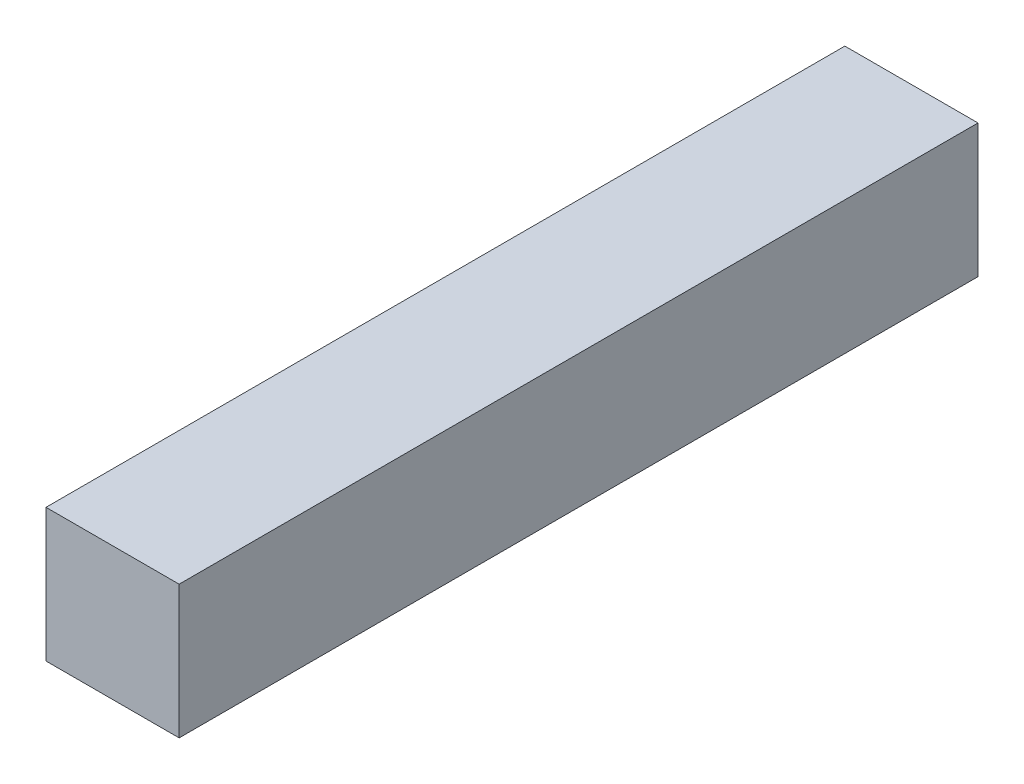
SolidWorks part; units mm, degrees
ref_plane "Front Plane" through (0, 0, 0) normal (0, 0, 1) x (1, 0, 0)
ref_plane "Top Plane" through (0, 0, 0) normal (0, 1, 0) x (1, 0, 0)
ref_plane "Right Plane" through (0, 0, 0) normal (1, 0, 0) x (0, 0, -1)
sketch "Sketch1" plane through (0, 0, 0) normal (0, 0, 1) x (1, 0, 0)
  line L3 (1.5, -1.5) -> (-1.5, -1.5)
  line L4 (1.5, -1.5) -> (1.5, 1.5)
  line L5 (1.5, 1.5) -> (-1.5, 1.5)
  line L6 (-1.5, -1.5) -> (-1.5, 1.5)
  line L7 (1.5, -1.5) -> (-1.5, 1.5) construction
  line L8 (1.5, 1.5) -> (-1.5, -1.5) construction
  point P0 (0, 0)
  dimension "Width" = 3
  dimension "Height" = 3
sketch "Sketch2" plane through (0, 0, 0) normal (1, 0, 0) x (0, 0, -1)
  line L2 (9, -1.5) -> (-9, -1.5)
  line L3 (9, -1.5) -> (9, 1.5)
  line L4 (9, 1.5) -> (-9, 1.5)
  line L5 (-9, -1.5) -> (-9, 1.5)
  line L6 (9, -1.5) -> (-9, 1.5) construction
  line L7 (9, 1.5) -> (-9, -1.5) construction
  point P0 (0, 0)
  point P4 (0, 0)
  point P15 (-5.7, 1.5)
  point P17 (5.7, 1.5)
  dimension "Length" = 18
  dimension "D1" = 3.3
  dimension "D2" = 3.3
sketch "Sketch3" plane through (0, 0, 0) normal (0, 0, 1) x (1, 0, 0)
  line L0 (1.5, -1.5) -> (1.5, 1.5) construction
  line L5 (1.5, -1.5) -> (-1.5, -1.5) construction
  line L6 (-1.5, -1.5) -> (-1.5, 1.5) construction
  line L7 (1.5, 1.5) -> (-1.5, 1.5) construction
  line L8 (1.5, -1.5) -> (1.5, 1.5)
  line L9 (1.5, -1.5) -> (-1.5, -1.5)
  line L10 (-1.5, -1.5) -> (-1.5, 1.5)
  line L11 (1.5, 1.5) -> (-1.5, 1.5)
extrude "Boss-Extrude1" add sketch "Sketch3" along normal up to vertex (9 mm away) and the other way up to vertex (9 mm away) up to point (0, 1.5, 9) other way up to point (0, 1.5, -9)
fillet "Fillet2" [suppressed] radius 0.15
ref_plane "Contact Plane 1" through (0, 0, 9) normal (0, 0, 1) x (1, 0, 0)
ref_plane "Contact Plane 2" through (0, 0, -9) normal (0, 0, 1) x (1, 0, 0)
ref_axis "Center Axis 1" through (0, 0, -27.5) along (0, 0, 1)
equation "\"D1@Sketch2\"=\"Width@Sketch1\"*1.1"
equation "\"D2@Sketch2\"=\"D1@Sketch2\""
